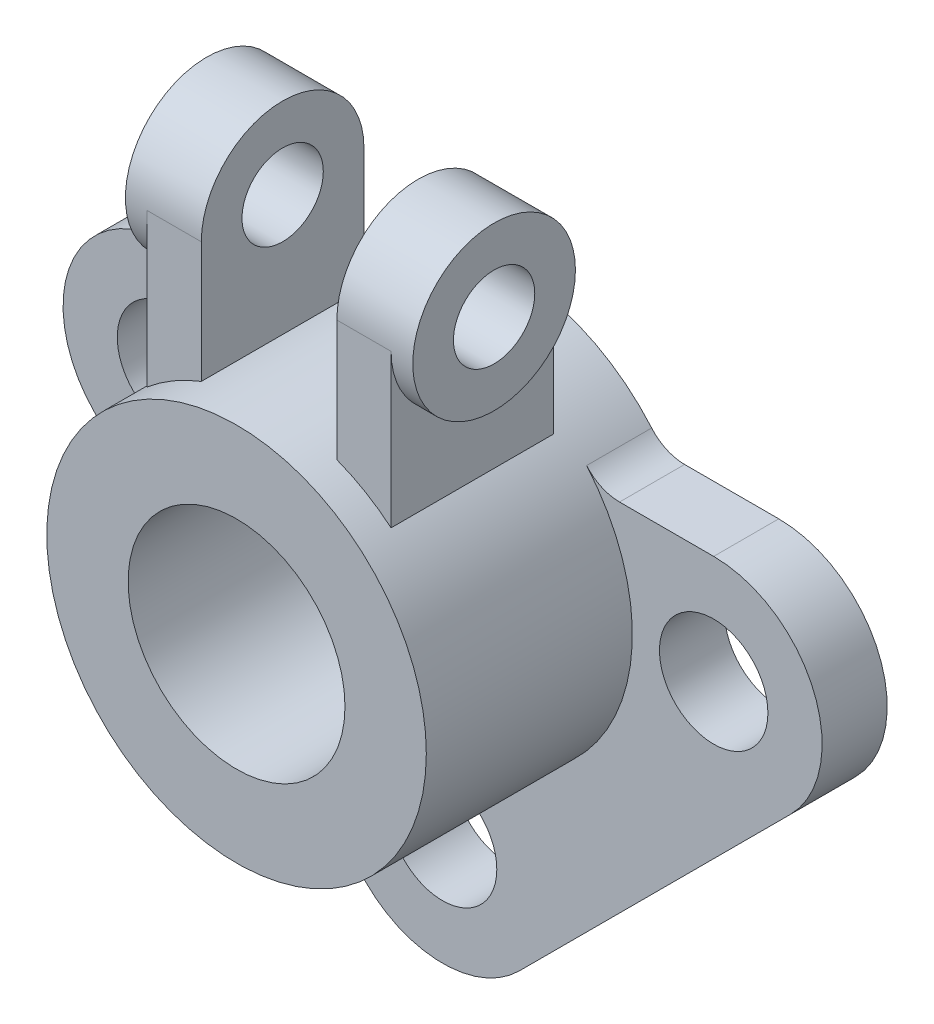
SolidWorks part; units mm, degrees
material "Alloy Steel"
ref_plane "Front Plane" through (0, 0, 0) normal (0, 0, 1) x (1, 0, 0)
ref_plane "Top Plane" through (0, 0, 0) normal (0, 1, 0) x (1, 0, 0)
ref_plane "Right Plane" through (0, 0, 0) normal (1, 0, 0) x (0, 0, -1)
sketch "Sketch1" plane through (0, 0, 0) normal (0, 0, 1) x (1, 0, 0)
  line L0 (0, 0) -> (0, -50) construction
  line L1 (0, 0) -> (0, 55) construction
  line L2 (-50, 20) -> (50, 20)
  line L3 (64.1421, -14.1421) -> (14.1421, -64.1421)
  line L4 (-14.1421, -64.1421) -> (-64.1421, -14.1421)
  arc A0 (50, 20) -> (64.1421, -14.1421) centre (50, 0) cw
  arc A1 (-50, 20) -> (-64.1421, -14.1421) centre (-50, 0) ccw
  arc A2 (14.1421, -64.1421) -> (-14.1421, -64.1421) centre (0, -50) cw
  circle A3 centre (0, -50) radius 10
  circle A4 centre (-50, 0) radius 10
  circle A5 centre (50, 0) radius 10
  circle A6 centre (0, 0) radius 35
  circle A7 centre (0, 0) radius 20
  point P15 (0, 20)
  dimension "D3" = 20
  dimension "D4" = 20
  dimension "D5" = 20
  dimension "D6" = 20
  dimension "D9" = 70
  dimension "D10" = 40
  dimension "D1" = 55
  dimension "D2" = 50
  dimension "D7" = 50
  dimension "D8" = 100
extrude "Boss-Extrude1" add sketch "Sketch1" along normal blind 12 contours A6 L2 A1 L4 A2 L3 A0 A5 A4 A3 region at (-39.3614, 18.3357, 0)
extrude "Boss-Extrude2" add sketch "Sketch1<3>" along normal blind 50 contours L2 A7 A6 | L2 A6 region at (0, 26.126, 0) region at (-14.3614, 19.1098, 0)
sketch "Sketch1<3>" plane through (0, 0, 0) normal (0, 0, 1) x (1, 0, 0) same geometry as "Sketch1"
fillet "Fillet1" radius 8 2 edges at (-28.7228, 20, 6) (28.7228, 20, 6)
sketch "Sketch2" plane through (0, 0, 0) normal (1, 0, 0) x (0, 0, -1)
  line L0 (-50, 35) -> (-44, 35) construction
  line L1 (0, 35) -> (-50, 35) construction
  line L4 (-50, 35) -> (-50, -35) construction
  line L5 (-44, 35) -> (-44, 20.9544)
  line L6 (-44, 20.9544) -> (-14, 20.9544)
  line L7 (-14, 20.9544) -> (-14, 55)
  line L8 (-14, 55) -> (-44, 55)
  line L9 (-44, 55) -> (-44, 35)
  dimension "D1" = 6
  dimension "D2" = 30
  dimension "D3" = 55
extrude "Boss-Extrude3" add sketch "Sketch2" along normal blind 10 from offset 12.5
sketch "Sketch3" plane through (22.5, 0, 0) normal (1, 0, 0) x (0, 0, -1)
  line L0 (-14, 55) -> (-44, 55) construction
  circle A0 centre (-29, 55) radius 15
extrude "Boss-Extrude4" add sketch "Sketch3" along normal blind 4 and the other way blind 10
sketch "Sketch4" plane through (26.5, 0, 0) normal (1, 0, 0) x (0, 0, -1)
  circle A0 centre (-29, 55) radius 7.5
  dimension "D1" = 15
extrude "Cut-Extrude1" cut sketch "Sketch4" against normal up to next
mirror "Mirror1" about plane through (0, 0, 0) normal (1, 0, 0) of bodies 105
